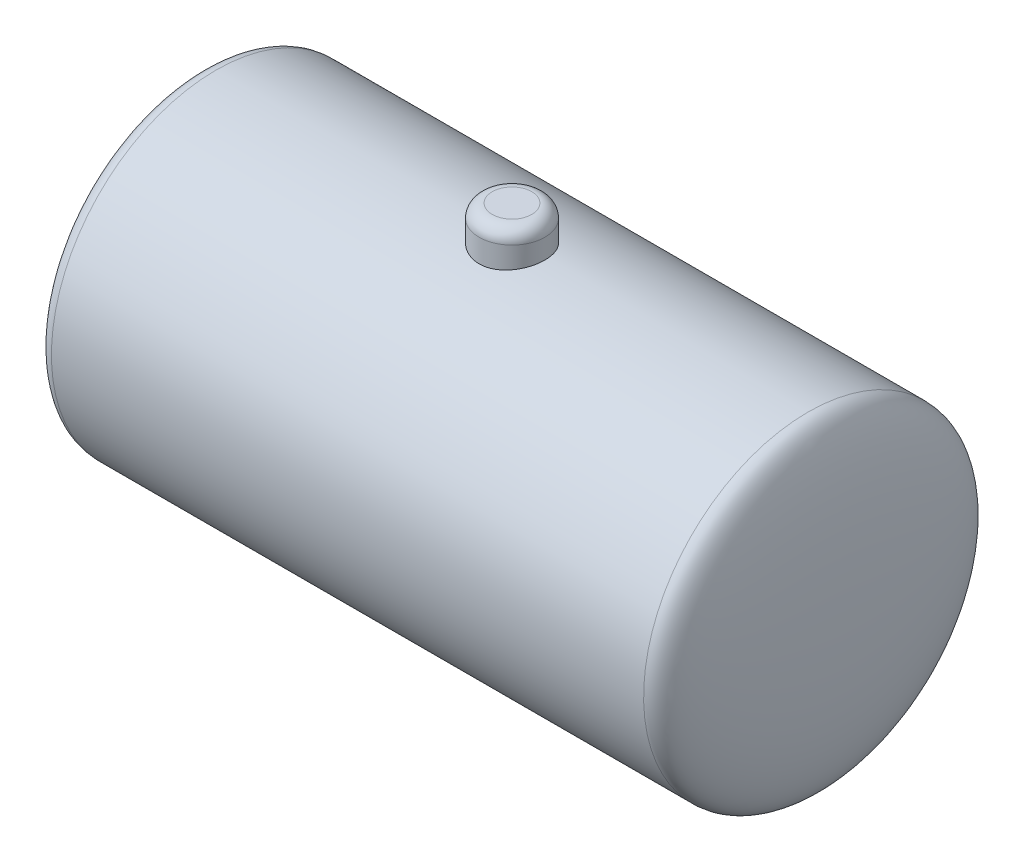
SolidWorks part; units mm, degrees
material "Cast Alloy Steel"
ref_plane "Front Plane" through (0, 0, 0) normal (0, 0, 1) x (1, 0, 0)
ref_plane "Top Plane" through (0, 0, 0) normal (0, 1, 0) x (1, 0, 0)
ref_plane "Right Plane" through (0, 0, 0) normal (1, 0, 0) x (0, 0, -1)
sketch "Sketch1" plane through (0, 0, 0) normal (1, 0, 0) x (0, 0, -1)
  circle A0 centre (0, 0) radius 25
  dimension "D1" = 50
extrude "Boss-Extrude1" add sketch "Sketch1" along normal mid plane 90 contours A0
sketch "Sketch2" plane through (0, 0, 0) normal (0, 0, 1) x (1, 0, 0)
  line L1 (-45, 25) -> (-45, -25) construction
  line L2 (-45, 25) -> (-50, 25) construction
  line L3 (-50, 25) -> (-50, 0) construction
  line L4 (-45, 25) -> (-45, 0)
  line L5 (-45, 25) -> (-45, 0)
  line L6 (-45, 0) -> (-50, 0)
  line L7 (45, 25) -> (-45, 25) construction
  line L8 (0, -11.4539) -> (0, 15.6189) construction
  line L9 (45, 25) -> (50, 25) construction
  line L10 (50, 25) -> (50, 0) construction
  line L11 (45, 0) -> (50, 0)
  line L12 (45, 25) -> (45, 0)
  spline S0 degree 2 poles (-45, 25) (-50, 25) (-50, 0) knots 0 0 0 1 1 1
  spline S1 degree 2 poles (45, 25) (50, 25) (50, 0) knots 0 0 0 1 1 1
  dimension "D1" = 5
revolve "Revolve1" add sketch "Sketch2" angle 360 about L6 region at (-47.2, 11, 0)
revolve "Revolve2" add sketch "Sketch2<4>" angle 360 about L11 region at (47.2, 11, 0)
sketch "Sketch2<4>" plane through (0, 0, 0) normal (0, 0, 1) x (1, 0, 0) same geometry as "Sketch2"
sketch "Sketch3" plane through (0, 0, 0) normal (0, 1, 0) x (1, 0, 0)
  circle A0 centre (0, 0) radius 5
  dimension "D1" = 10
extrude "Boss-Extrude2" add sketch "Sketch3" along normal blind 30
fillet "Fillet1" radius 2 1 edges at (0, 30, 5)
sketch "Sketch4" plane through (0, 0, 0) normal (0, 1, 0) x (1, 0, 0)
  line L0 (-31.9571, 0) -> (24.4902, 0) construction
  circle A0 centre (-25, 0) radius 2.5
  circle A1 centre (25, 0) radius 2.5
  dimension "D1" = 5
  dimension "D2" = 25
  dimension "D3" = 50
extrude "Boss-Extrude3" add sketch "Sketch4" against normal blind 30
chamfer "Chamfer1" distance 1 angle 45 2 edges at (25, -30, 2.5) (-25, -30, 2.5)
